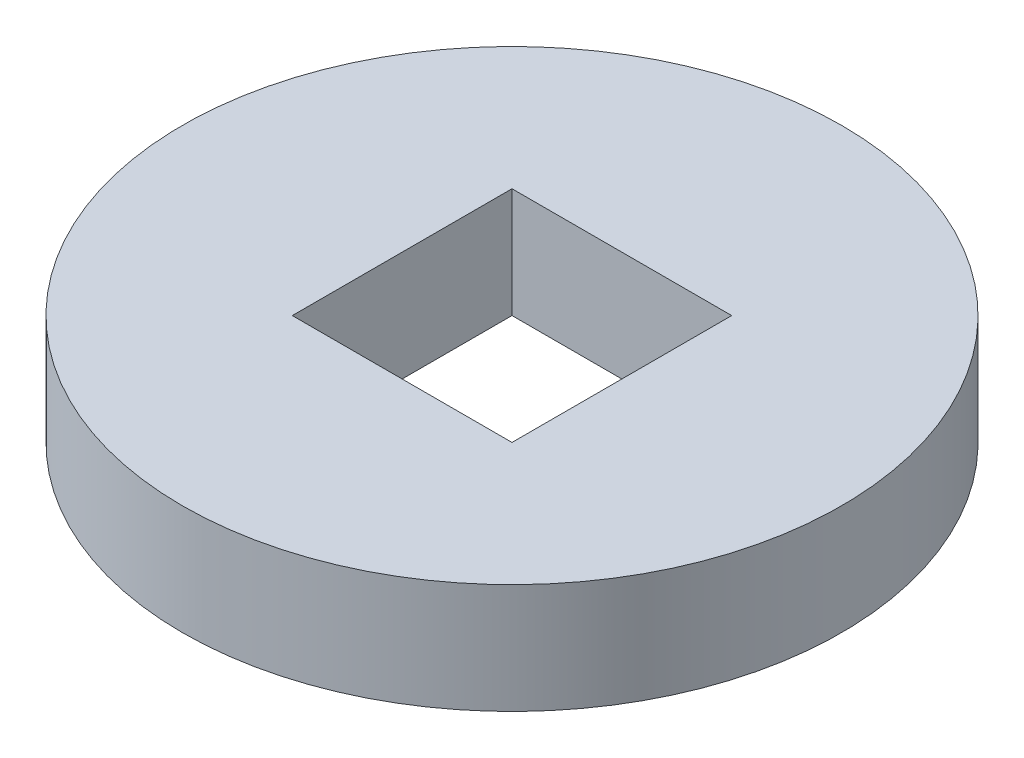
SolidWorks part; units mm, degrees
ref_plane "Front Plane" through (0, 0, 0) normal (0, 0, 1) x (1, 0, 0)
ref_plane "Top Plane" through (0, 0, 0) normal (0, 1, 0) x (1, 0, 0)
ref_plane "Right Plane" through (0, 0, 0) normal (1, 0, 0) x (0, 0, -1)
sketch "Sketch1" plane through (0, 0, 0) normal (0, 1, 0) x (1, 0, 0)
  line L0 (0, 15) -> (11.9476, 15) construction
  line L1 (5, -5) -> (-5, -5)
  line L2 (5, -5) -> (5, 5)
  line L3 (5, 5) -> (-5, 5)
  line L4 (-5, -5) -> (-5, 5)
  line L5 (5, -5) -> (-5, 5) construction
  line L6 (5, 5) -> (-5, -5) construction
  circle A0 centre (0, 0) radius 15
  dimension "D1" = 30
  dimension "D2" = 10
  dimension "D3" = 10
extrude "Boss-Extrude1" add sketch "Sketch1" along normal blind 5
